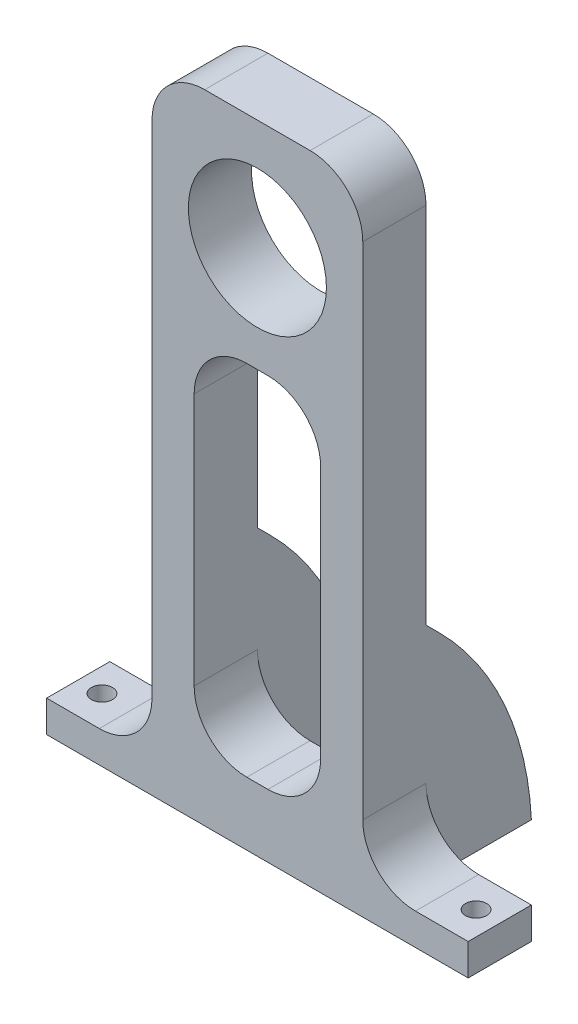
SolidWorks part; units mm, degrees
ref_plane "Ön Düzlem" through (0, 0, 0) normal (0, 0, 1) x (1, 0, 0)
ref_plane "Üst Düzlem" through (0, 0, 0) normal (0, 1, 0) x (1, 0, 0)
ref_plane "Sağ Düzlem" through (0, 0, 0) normal (1, 0, 0) x (0, 0, -1)
sketch "Çizim1" plane through (0, 0, 0) normal (0, 0, 1) x (1, 0, 0)
  line L0 (-162.231, 30.1944) -> (-162.231, -74.8056)
  line L1 (-162.231, -74.8056) -> (-182.231, -74.8056)
  line L2 (-182.231, -74.8056) -> (-182.231, -80.8056)
  line L3 (-182.231, -80.8056) -> (-102.231, -80.8056)
  line L4 (-102.231, -80.8056) -> (-102.231, -74.8056)
  line L5 (-102.231, -74.8056) -> (-122.231, -74.8056)
  line L6 (-122.231, -74.8056) -> (-122.231, 30.1944)
  line L7 (-132.231, 40.1944) -> (-152.231, 40.1944)
  line L9 (-144.231, -0.8056) -> (-140.231, -0.8056)
  line L10 (-154.231, -10.8056) -> (-154.231, -58.8056)
  line L11 (-144.231, -68.8056) -> (-140.231, -68.8056)
  line L12 (-130.231, -10.8056) -> (-130.231, -58.8056)
  circle A0 centre (-142.231, 19.1944) radius 13.1
  arc A1 (-122.231, 30.1944) -> (-132.231, 40.1944) centre (-132.231, 30.1944) ccw
  arc A2 (-162.231, 30.1944) -> (-152.231, 40.1944) centre (-152.231, 30.1944) cw
  arc A3 (-140.231, -68.8056) -> (-130.231, -58.8056) centre (-140.231, -58.8056) ccw
  arc A4 (-144.231, -68.8056) -> (-154.231, -58.8056) centre (-144.231, -58.8056) cw
  arc A5 (-130.231, -10.8056) -> (-140.231, -0.8056) centre (-140.231, -10.8056) ccw
  arc A6 (-154.231, -10.8056) -> (-144.231, -0.8056) centre (-144.231, -10.8056) cw
  point P10 (-142.231, 40.1944)
  point P14 (-122.231, 40.1944)
  point P17 (-162.231, 40.1944)
  dimension "D1" = 26.2
  dimension "D9" = 10
  dimension "D14" = 10
  dimension "D2" = 80
  dimension "D3" = 40
  dimension "D4" = 0
  dimension "D5" = 100
  dimension "D6" = 115
  dimension "D7" = 6
  dimension "D8" = 20
  dimension "D10" = 8
  dimension "D11" = 8
  dimension "D12" = 12
  dimension "D13" = 20
extrude "Yükseklik-Ekstrüzyon1" add sketch "Çizim1" along normal blind 12
fillet "Radyus1" radius 10 1 edges at (-122.231, -74.8056, 6)
fillet "Radyus2" radius 10 1 edges at (-162.231, -74.8056, 6)
sketch "Çizim2" plane through (0, -74.8056, 0) normal (0, 1, 0) x (1, 0, 0)
  line L0 (-182.231, -12) -> (-182.231, 0) construction
  line L1 (-102.231, -12) -> (-102.231, 0) construction
  circle A0 centre (-106.731, -6) radius 2
  circle A1 centre (-177.731, -6) radius 2
  dimension "D3" = 4
  dimension "D4" = 4
  dimension "D1" = 4.5
  dimension "D2" = 4.5
extrude "Kes-Ekstrüzyon1" cut sketch "Çizim2" against normal blind 12
sketch "Çizim3" plane through (0, 0, 0) normal (0, 0, -1) x (-1, 0, 0)
  line L0 (122.231, -64.8056) -> (122.231, 30.1944) construction
  line L1 (122.231, -58.8056) -> (130.231, -58.8056)
  line L2 (122.231, -58.8056) -> (122.231, -80.8056)
  line L3 (122.231, -80.8056) -> (130.231, -80.8056)
  line L4 (130.231, -58.8056) -> (130.231, -80.8056)
  line L5 (182.231, -80.8056) -> (102.231, -80.8056) construction
  line L7 (154.231, -58.8056) -> (162.231, -58.8056)
  line L8 (154.231, -58.8056) -> (154.231, -80.8056)
  line L9 (154.231, -80.8056) -> (162.231, -80.8056)
  line L10 (162.231, -58.8056) -> (162.231, -80.8056)
extrude "Yükseklik-Ekstrüzyon2" add sketch "Çizim3" along normal blind 20
chamfer "Pah1" distance 20 angle 45 2 edges at (-158.231, -58.8056, 0) (-126.231, -58.8056, 0)
fillet "Radyus3" radius 60 2 edges at (-126.231, -58.8056, -20) (-158.231, -58.8056, -20)
